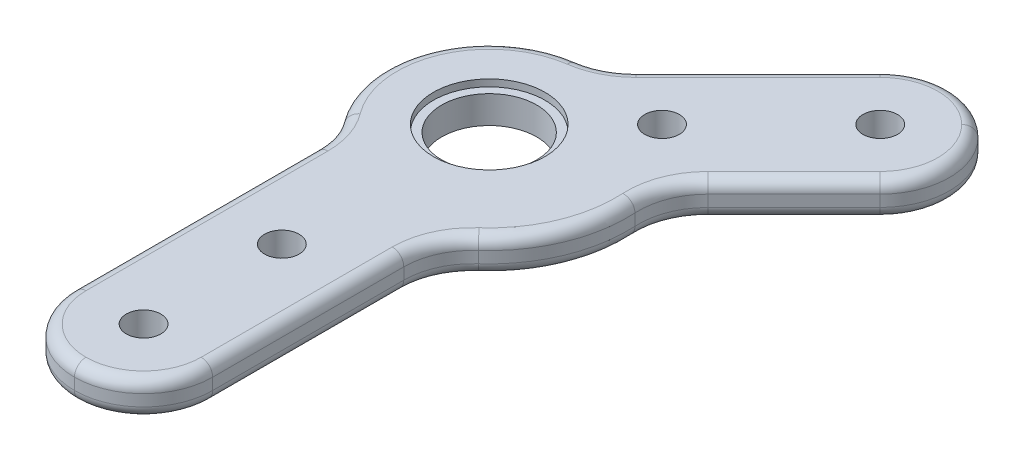
SolidWorks part; units mm, degrees
material "6061 Alloy"
ref_plane "Front Plane" through (0, 0, 0) normal (0, 0, 1) x (1, 0, 0)
ref_plane "Top Plane" through (0, 0, 0) normal (0, 1, 0) x (1, 0, 0)
ref_plane "Right Plane" through (0, 0, 0) normal (1, 0, 0) x (0, 0, -1)
sketch "Sketch1" plane through (0, 0, 0) normal (0, 1, 0) x (1, 0, 0)
  line L0 (0, 44.45) -> (0, -44.45) construction
  line L1 (-12.7, -44.45) -> (12.7, -44.45)
  line L2 (-12.7, -44.45) -> (-12.7, 31.75)
  line L3 (-12.7, 44.45) -> (12.7, 44.45) construction
  line L4 (12.7, -44.45) -> (12.7, 31.75)
  line L5 (-12.7, -44.45) -> (12.7, 44.45) construction
  line L6 (-12.7, 44.45) -> (12.7, -44.45) construction
  line L7 (0, 31.75) -> (44.9013, 76.6513) construction
  line L8 (8.9803, 22.7697) -> (53.8815, 67.671)
  line L9 (53.8815, 67.671) -> (35.921, 85.6315)
  line L10 (35.921, 85.6315) -> (-8.9803, 40.7303)
  line L11 (-8.9803, 40.7303) -> (8.9803, 22.7697) construction
  line L12 (12.7, 44.45) -> (12.7, 31.75) construction
  line L13 (12.7, 44.45) -> (12.7, 62.4105) construction
  circle A0 centre (0, 31.75) radius 12.7 construction
  circle A1 centre (0, -31.75) radius 3.175
  circle A2 centre (0, -6.35) radius 3.175
  circle A3 centre (0, 31.75) radius 8.7312
  circle A4 centre (35.921, 67.671) radius 3.175
  circle A5 centre (15.875, 47.625) radius 3.175
  circle A6 centre (0, 31.75) radius 19.05
  arc A7 (24.5345, 38.324) -> (12.7, 9.753) centre (0, 31.75) cw
  point P0 (0, 0)
  point P16 (44.9013, 76.6513)
  point P21 (0, 31.75)
  dimension "D4" = 12.7
  dimension "D1" = 6.35
  dimension "D7" = 50.8
  dimension "D8" = 12.7
  dimension "D9" = 17.4625
  dimension "D10" = 6.35
  dimension "D11" = 6.35
  dimension "D2" = 25.4
  dimension "D3" = 45
  dimension "D5" = 25.4
  dimension "D6" = 38.1
extrude "Boss-Extrude1" add sketch "Sketch1" along normal blind 6.35 contours A0 L2 L1 L4 L8 A2 A1 | A0 A3 | A0 L4 L8 L9 L10 A4 | A0 L8 L4 | L4 A6 L8 | A7 L8 A6 L4 region at (0, 0, 14.9202) region at (-17.1023, 0, -38.834) region at (19.6895, 0, -23.5944) region at (28.7883, 0, -60.5383) region at (15.553, 0, -25.3078)
fillet "Fillet2" radius 12.7 8 edges at (35.921, 3.175, -85.6315) (53.8815, 3.175, -67.671) (-12.7, 3.175, 44.45) (12.7, 3.175, 44.45) (1.06, 3.175, -50.7705) (-12.7, 3.175, -17.551) (12.7, 3.175, -9.753) (24.5345, 3.175, -38.324)
fillet "Fillet3" radius 2.1167 28 edges at (12.7, 0, 14.199) (8.9803, 0, 40.7303) (-8.9803, 0, 40.7303) (-12.7, 0, 9.525) (15.7154, 0, -65.426) (35.921, 0, -80.371) (48.621, 0, -67.671) (12.7, 6.35, 14.199) (8.9803, 6.35, 40.7303) (-8.9803, 6.35, 40.7303) (-12.7, 6.35, 9.525) (15.7154, 6.35, -65.426) (35.921, 6.35, -80.371) (48.621, 6.35, -67.671) (36.981, 0, -50.7705) (36.981, 6.35, -50.7705) (-13.3517, 0, -16.7161) (-17.5999, 0, -39.0401) (1.1895, 0, -51.8217) (-13.3517, 6.35, -16.7161) (-17.5999, 6.35, -39.0401) (1.1895, 6.35, -51.8217) (26.177, 0, -38.4016) (23.4665, 0, -22.0298) (13.8065, 0, -8.5367) (26.177, 6.35, -38.4016) (23.4665, 6.35, -22.0298) (13.8065, 6.35, -8.5367)
sketch "Sketch2" plane through (0, 6.35, 0) normal (0, 1, 0) x (1, 0, 0)
  circle A0 centre (0, 31.75) radius 10.2489
  dimension "D1" = 20.4978
extrude "Cut-Extrude1" cut sketch "Sketch2" against normal blind 1.27
